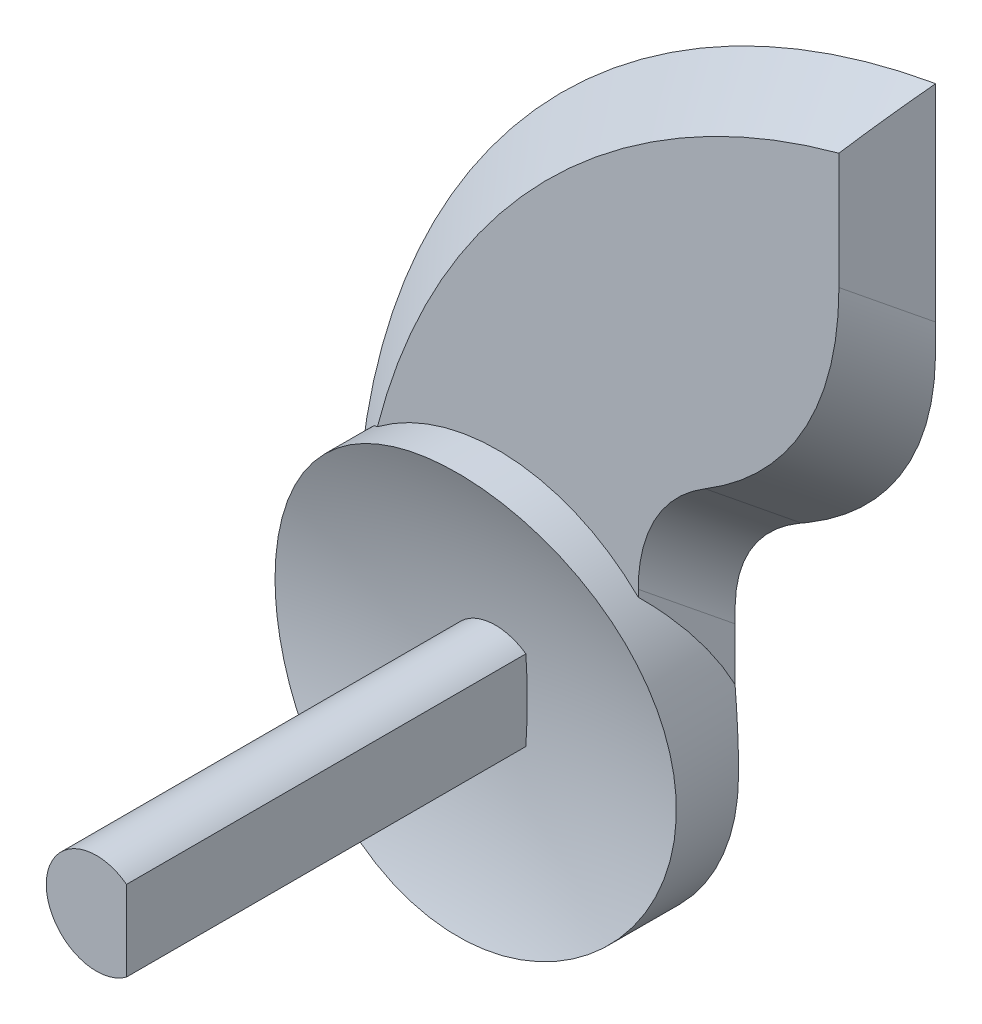
SolidWorks part; units mm, degrees
ref_plane "Front Plane" through (0, 0, 0) normal (0, 0, 1) x (1, 0, 0)
ref_plane "Top Plane" through (0, 0, 0) normal (0, 1, 0) x (1, 0, 0)
ref_plane "Right Plane" through (0, 0, 0) normal (1, 0, 0) x (0, 0, -1)
sketch "Sketch1" plane through (0, 0, 0) normal (0, 0, 1) x (1, 0, 0)
  line L0 (10, 0) -> (10, 10)
  line L1 (10, 10) -> (20, 15)
  line L2 (20, 15) -> (20, 35)
  circle A0 centre (0, 0) radius 10
  arc A1 (-10, 0) -> (20, 35) centre (25.4167, 0) cw
  dimension "D1" = 20
  dimension "D2" = 20
  dimension "D3" = 5
  dimension "D4" = 10
  dimension "D5" = 35
extrude "Boss-Extrude1" add sketch "Sketch1" along normal blind 4 contours A1 A0 L0 L1 L2 | A0
chamfer "Chamfer1" distance 2 angle 55 5 edges at (10, 5, 0) (0, -10, 0) (15, 12.5, 0) (20, 25, 0) (-1.4737, 23.0489, 0)
sketch "Sketch3" plane through (0, 0, 4) normal (0, 0, 1) x (1, 0, 0)
  circle A0 centre (0, 0) radius 10
  dimension "D1" = 20
extrude "Boss-Extrude2" add sketch "Sketch3" along normal blind 2
sketch "Sketch4" plane through (0, 0, 0) normal (1, 0, 0) x (0, 0, -1)
  line L3 (-50, 16.6132) -> (-50, -16.6132)
  arc A1 (-50, 16.6132) -> (-50, -16.6132) centre (-30, 0) cw
  point P10 (-4, 0)
  dimension "D1" = 4
  dimension "D2" = 50
revolve "Cut-Revolve2" cut sketch "Sketch4" angle 360 about L3
chamfer "Chamfer2" distance 3 angle 45 4 edges at (10, 5, 4) (15, 12.5, 4) (20, 25, 4) (-1.4737, 23.0489, 4)
sketch "Sketch5" plane through (0, 0, 0) normal (0, 0, -1) x (-1, 0, 0)
  line L0 (-1.5, 2) -> (-1.5, -2)
  circle A0 centre (0, 0) radius 2.5
  dimension "D1" = 5
  dimension "D2" = 1.5
extrude "Boss-Extrude3" add sketch "Sketch5" against normal blind 24 contours L0 A0
sketch "Sketch6" plane through (0, 0, 0) normal (0, 0, -1) x (-1, 0, 0)
  circle A0 centre (0, 0) radius 7.1437
extrude "Boss-Extrude4" add sketch "Sketch6" along normal blind 2
chamfer "Chamfer3" distance 2 angle 60 1 edges at (-7.1437, 0, -2)
fillet "Fillet1" radius 10 2 edges at (8.2059, 11.1088, 2.7941) (8.2778, 11.0644, 0.7941)
fillet "Fillet2" radius 20 2 edges at (18.2778, 16.0644, 0.7941) (18.2059, 16.1088, 2.7941)
